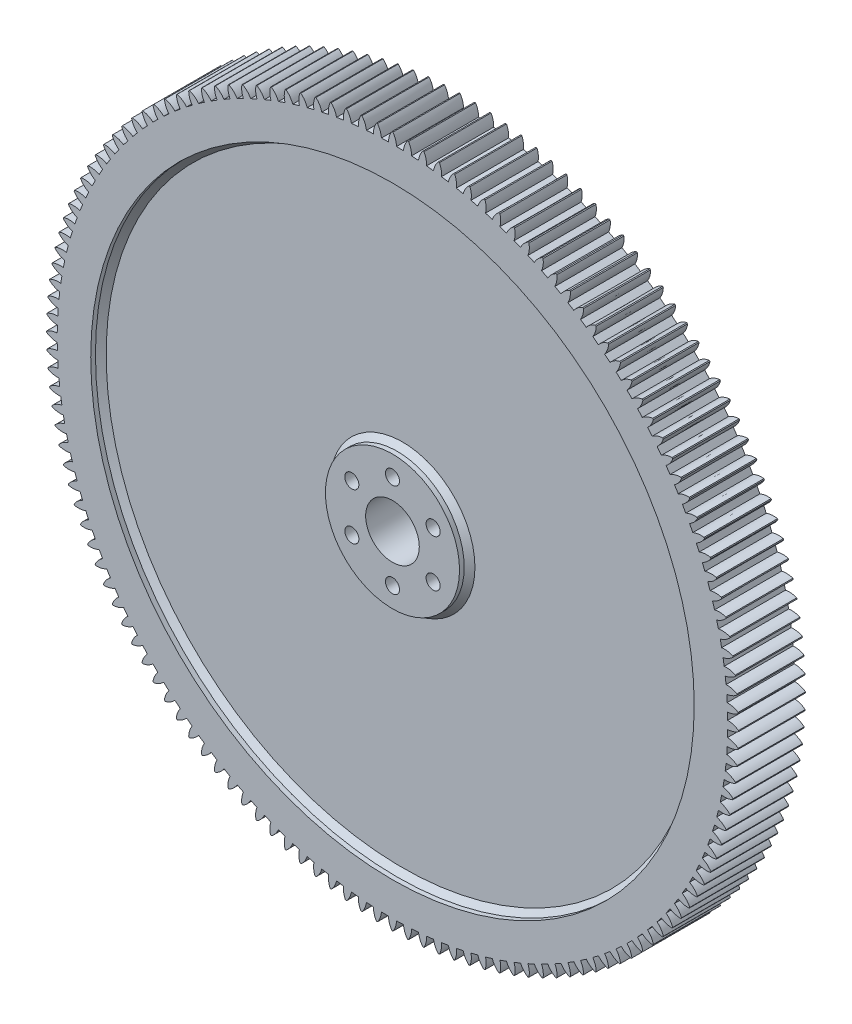
SolidWorks part; units mm, degrees
material "Cast iron, gray, flake graphite, EN GJL 250"
ref_plane "Front Plane" through (0, 0, 0) normal (0, 0, 1) x (1, 0, 0)
ref_plane "Top Plane" through (0, 0, 0) normal (0, 1, 0) x (1, 0, 0)
ref_plane "Right Plane" through (0, 0, 0) normal (1, 0, 0) x (0, 0, -1)
sketch "Sketch8" plane through (0, 0, 0) normal (0, 0, 1) x (1, 0, 0)
  circle A0 centre (0, 0) radius 225
  circle A1 centre (0, 0) radius 250
  dimension "D1" = 500
  dimension "D2" = 450
extrude "Boss-Extrude1" add sketch "Sketch8" along normal mid plane 50
sketch "Sketch9" plane through (0, 0, 0) normal (0, 0, 1) x (1, 0, 0)
  circle A0 centre (0, 0) radius 50
  dimension "D1" = 100
extrude "Boss-Extrude2" add sketch "Sketch9" along normal mid plane 50 separate body
sketch "Sketch10" plane through (0, 0, 0) normal (0, 0, 1) x (1, 0, 0)
  circle A0 centre (0, 0) radius 50
  circle A1 centre (0, 0) radius 225
  circle A2 centre (0, 0) radius 50 construction
  circle A3 centre (0, 0) radius 225 construction
extrude "Boss-Extrude3" add sketch "Sketch10" along normal mid plane 35
chamfer "Chamfer2" distance 4 angle 45 4 edges at (225, 0, 17.5) (50, 0, 17.5) (225, 0, -17.5) (50, 0, -17.5)
sketch "Sketch11" plane through (0, 0, 25) normal (0, 0, 1) x (1, 0, 0)
  circle A0 centre (0, 0) radius 20
  dimension "D1" = 40
extrude "Cut-Extrude1" cut sketch "Sketch11" against normal through all
ref_axis "Axis1" through (0, 0, -12.82) along (0, 0, 1)
sketch "Sketch13" plane through (0, 0, 25) normal (0, 0, 1) x (1, 0, 0)
  line L0 (-0.375, 258) -> (0.375, 258)
  line L1 (4.7384, 265.3027) -> (-5.4884, 250.6973) construction
  line L2 (0, 258) -> (0, 250) construction
  circle A0 centre (0, 0) radius 250 construction
  arc A1 (3, 249.982) -> (-3, 249.982) centre (0, 0) ccw
  spline S0 degree 2 poles (-3, 249.982) (-2.8086, 254.5245) (-0.375, 258) knots 0 0 0 0.951846 0.951846 0.951846
  spline S1 degree 2 poles (3, 249.982) (2.8086, 254.5245) (0.375, 258) knots 0 0 0 0.951846 0.951846 0.951846
  dimension "D1" = 55
  dimension "D3" = 8
  dimension "D4" = 6
  dimension "D5" = 8.4857
  dimension "D2" = 0.75
extrude "Boss-Extrude4" add sketch "Sketch13" against normal up to surface (50 mm away) up to face at (250, 0, -25)
pattern_circular "CirPattern2" count 140 over 360 about axis through (0, 0, 25) along (0, 0, -1) of "Boss-Extrude4"
hole_wizard "M12x1.5 Tapped Hole1" positions "Sketch14" profile "Sketch15" tap size "M12x1.5" standard "ANSI Metric" end condition through all
sketch "Sketch14" plane through (0, 0, 25) normal (0, 0, 1) x (1, 0, 0)
  line L1 (0, 20) -> (0, 50) construction
  circle A4 centre (0, 0) radius 50 construction
  circle A5 centre (0, 0) radius 20 construction
  point P127 (0, 35)
  point P130 (0, 0)
  point P133 (0, 0)
  point P134 (0, 0)
  point P135 (0, 0)
  point P136 (0, 35)
  point P137 (0, 35)
cosmetic thread "Hole Thread1" parameters "D2"=12
sketch "Sketch15" plane through (0, 35, 25) normal (1, 0, 0) x (0, -1, 0)
  line L0 (0, 0) -> (0, 50)
  line L1 (0, 50) -> (5.25, 50)
  line L2 (5.25, 50) -> (5.25, 0)
  line L5 (5.25, 0) -> (0, 0)
  line L11 (0, -6.35) -> (0, 107.95) construction
  dimension "Thru Tap Drill Dia." = 10.5
  dimension "Thru Tap Drill Depth" = 50
pattern_circular "CirPattern3" count 6 over 360 about axis through (0, 0, -12.82) along (0, 0, 1) of "M12x1.5 Tapped Hole1"
cosmetic thread "Hole Thread2" parameters "D2"=12
cosmetic thread "Hole Thread3" parameters "D2"=12
cosmetic thread "Hole Thread4" parameters "D2"=12
cosmetic thread "Hole Thread5" parameters "D2"=12
cosmetic thread "Hole Thread6" parameters "D2"=12
equation "\"Flywheel Diameter\"= 500mm"
equation "\"Crankshaft Radius\"= 40mm"
equation "\"Flywheel Thickness\"= 50mm"
equation "\"D1@Sketch8\"=\"Flywheel Diameter\""
equation "\"D2@Sketch8\"=\"Flywheel Diameter\"-50mm"
equation "\"D1@Boss-Extrude1\"=\"Flywheel Thickness\""
equation "\"Hub Diameter\"= \"Crankshaft Radius\" + 60mm"
equation "\"D1@Sketch9\"=\"Hub Diameter\""
equation "\"D1@Boss-Extrude2\"=\"Flywheel Thickness\""
equation "\"D1@Boss-Extrude3\"=\"Flywheel Thickness\"*0.7"
equation "\"D1@Sketch11\"=\"Crankshaft Radius\""
